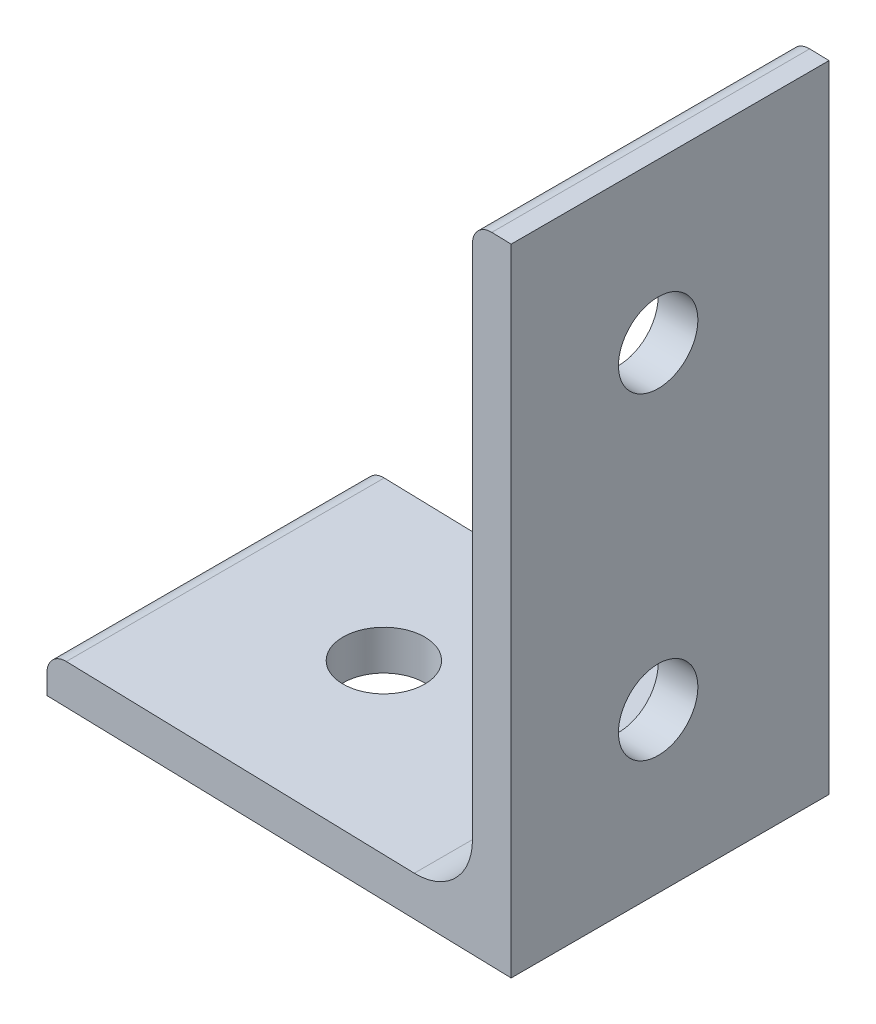
SolidWorks part; units mm, degrees
ref_plane "Front Plane" through (0, 0, 0) normal (0, 0, 1) x (1, 0, 0)
ref_plane "Top Plane" through (0, 0, 0) normal (0, 1, 0) x (1, 0, 0)
ref_plane "Right Plane" through (0, 0, 0) normal (1, 0, 0) x (0, 0, -1)
sketch "Sketch0" plane through (0, 0, 0) normal (0, 0, 1) x (1, 0, 0)
  line L0 (-19.05, -25.4) -> (19.05, -25.4)
  line L1 (19.05, -25.4) -> (19.05, 25.4)
  line L2 (19.05, 0) -> (0, 0) construction
  line L3 (0, 0) -> (0, -25.4) construction
  line L4 (15.875, -17.4498) -> (15.875, 25.4) construction
  line L5 (11.0998, -22.225) -> (-19.05, -22.225) construction
  arc A0 (15.875, -17.4498) -> (11.0998, -22.225) centre (11.0998, -17.4498) cw
  point P3 (14.4764, -20.8264)
  dimension "Inside Corner Radius" = 4.7752
  dimension "Outside Height" = 50.8
  dimension "Inside Height" = 47.625
  dimension "Inside Width" = 34.925
  dimension "Wall Thickness" = 3.175
  dimension "D1" = 3.175
  dimension "Outside Width" = 38.1
sketch "Sketch1" plane through (0, 0, 0) normal (1, 0, 0) x (0, 0, -1)
  line L0 (15.875, 0) -> (-15.875, 0)
  point P4 (0, 0)
  dimension "Length" = 31.75
sketch "Sketch2" plane through (0, 0, 0) normal (0, 0, 1) x (1, 0, 0)
  line L0 (-19.05, -25.4) -> (19.05, -25.4)
  line L1 (19.05, -25.4) -> (19.05, 25.4)
  line L2 (19.05, 25.4) -> (15.875, 25.4) construction
  line L3 (15.875, 23.8125) -> (15.875, -17.4498)
  line L4 (11.0998, -22.225) -> (-17.4625, -22.225)
  line L5 (-19.05, -25.4) -> (-19.05, -22.225) construction
  line L6 (17.4625, 25.4) -> (19.05, 25.4)
  line L7 (-19.05, -23.8125) -> (-19.05, -25.4)
  line L8 (19.05, 0) -> (0, 0) construction
  line L9 (0, 0) -> (0, -25.4) construction
  arc A0 (15.875, 23.8125) -> (17.4625, 25.4) centre (17.4625, 23.8125) cw
  arc A1 (-19.05, -23.8125) -> (-17.4625, -22.225) centre (-17.4625, -23.8125) cw
  arc A2 (15.875, -17.4498) -> (11.0998, -22.225) centre (11.0998, -17.4498) cw
  dimension "Inside Radius" = 4.7752
  dimension "Height" = 50.8
  dimension "Width" = 38.1
  dimension "Thickness" = 3.175
extrude "Boss-Extrude1" add sketch "Sketch2" along normal mid plane 31.75
sketch "Break Locations" plane through (0, 0, 0) normal (1, 0, 0) x (0, 0, -1)
  line L0 (35.941, 0) -> (-35.941, 0)
  line L1 (-15.875, -25.4) -> (-15.875, 25.4) construction
  line L2 (15.875, -25.4) -> (15.875, 25.4) construction
  point P0 (27.305, 0)
  point P1 (-27.305, 0)
  point P10 (0, 0)
  point P11 (-35.941, 0)
  point P13 (35.941, 0)
  dimension "D1" = 43.18
  dimension "D2" = 43.18
  dimension "D3" = 51.816
sketch "Sketch3" plane through (0, -25.4, 0) normal (0, -1, 0) x (1, 0, 0)
  line L1 (19.05, 15.875) -> (19.05, -15.875) construction
  line L2 (-19.05, 13.9268) -> (-19.05, -11.4819)
  line L6 (19.05, 0) -> (5.5904, 0) construction
  line L7 (19.05, -10.4842) -> (19.05, 14.9245)
  line L8 (-19.05, -11.4819) -> (19.05, -10.4842)
  line L10 (-19.05, 13.9268) -> (19.05, 14.9245)
sketch "Sketch4" plane through (19.05, 0, 0) normal (1, 0, 0) x (0, 0, -1)
  line L0 (-15.875, -25.4) -> (-3.175, -25.4) construction
  line L1 (-15.875, -25.4) -> (15.875, -25.4) construction
  line L2 (-3.175, -25.4) -> (-3.175, -12.7) construction
  line L3 (-3.175, -12.7) -> (-3.175, 12.7) construction
  circle A0 centre (-3.175, 12.7) radius 3.175
  circle A1 centre (-3.175, -12.7) radius 3.175
  dimension "D1" = 12.7
  dimension "D2" = 12.7
  dimension "D3" = 25.4
extrude "Cut-Extrude1" cut sketch "Sketch4" against normal through all
extrude "Cut-Extrude2" cut sketch "Sketch3" against normal through all flip side to cut
hole_wizard "1/4 Clearance Hole1" positions "Sketch7" profile "Sketch8" hole size "1/4" standard "ANSI Inch" end condition through all
sketch "Sketch7" plane through (0, -25.4, 0) normal (0, -1, 0) x (-1, 0, 0)
  point P4 (4.8355, -1.2122)
sketch "Sketch8" plane through (-4.8355, -25.4, 1.2122) normal (1, 0, 0) x (0, 0, -1)
  line L0 (0, 0) -> (0, 50.8)
  line L1 (0, 50.8) -> (3.2639, 50.8)
  line L2 (3.2639, 50.8) -> (3.2639, 0)
  line L5 (3.2639, 0) -> (0, 0)
  line L11 (0, -6.35) -> (0, 107.95) construction
  dimension "Thru Hole Dia." = 6.5278
  dimension "Thru Hole Depth" = 50.8
sketch "Sketch9" plane through (15.875, 0, 0) normal (-1, 0, 0) x (0, 0, 1)
  circle A0 centre (3.175, -12.7) radius 6.35
extrude "Cut-Extrude3" cut sketch "Sketch9" along normal blind 2.54
equation "\"D1@Break Locations\" = .85 * \"Height@Sketch2\""
equation "\"D2@Break Locations\"=\"D1@Break Locations\""
equation "\"Thickness@Sketch2\"=\"wall thickness@sketch0\""
equation "\"Height@Sketch2\"=\"outside height@sketch0\""
equation "\"Width@Sketch2\"=\"outside width@sketch0\""
equation "\"Inside Radius@Sketch2\"=\"inside corner radius@sketch0\""
equation "\"Length@Boss-Extrude1\"=\"length@sketch1\""
equation "\"D3@Break Locations\"=\"D2@Break Locations\"*1.2"
equation "\"D1@Sketch0\"=\"Wall Thickness@Sketch0\""
